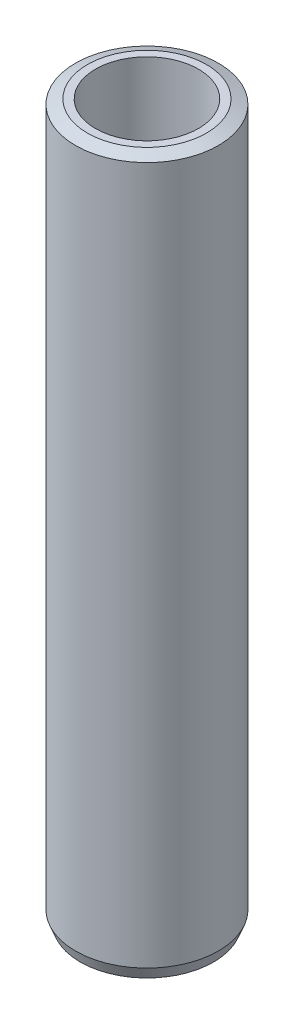
SolidWorks part; units mm, degrees
ref_plane "Front Plane" through (0, 0, 0) normal (0, 0, 1) x (1, 0, 0)
ref_plane "Top Plane" through (0, 0, 0) normal (0, 1, 0) x (1, 0, 0)
ref_plane "Right Plane" through (0, 0, 0) normal (1, 0, 0) x (0, 0, -1)
sketch "Sketch1" plane through (0, 0, 0) normal (0, 1, 0) x (1, 0, 0)
  circle A0 centre (0, 0) radius 60
  dimension "SHAFT_OD" = 120
extrude "Boss-Extrude1" add sketch "Sketch1" along normal blind 600
sketch "Sketch2" plane through (0, 0, 0) normal (0, 1, 0) x (1, 0, 0)
  circle A0 centre (0, 0) radius 43.2553
  dimension "BORE_D" = 86.5106
extrude "Cut-Extrude1" cut sketch "Sketch2" along normal through all
chamfer "Chamfer1" distance 3.9927 angle 68.312 2 edges at (0, 600, 60) (0, 0, 60) first distance on face at (0, 600, 60) first distance on face at (0, 0, 43.2553)
